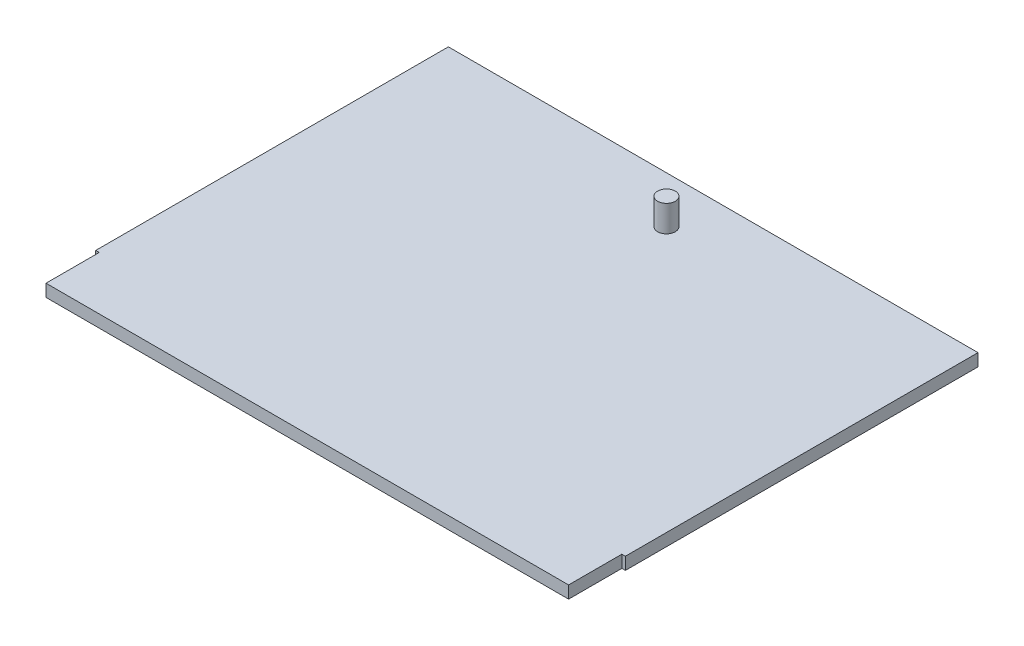
SolidWorks part; units mm, degrees
ref_plane "Front Plane" through (0, 0, 0) normal (0, 0, 1) x (1, 0, 0)
ref_plane "Top Plane" through (0, 0, 0) normal (0, 1, 0) x (1, 0, 0)
ref_plane "Right Plane" through (0, 0, 0) normal (1, 0, 0) x (0, 0, -1)
sketch "Sketch1" plane through (0, 0, 0) normal (0, 1, 0) x (1, 0, 0)
  line L0 (-5.476, 107.7101) -> (-5.476, 7.7101)
  line L1 (-5.476, 107.7101) -> (144.724, 107.7101)
  line L3 (-4.476, -7.3899) -> (143.724, -7.3899)
  line L4 (144.724, 107.7101) -> (144.724, 7.7101)
  line L5 (-5.476, 7.7101) -> (-4.476, 7.7101)
  line L6 (-4.476, 7.7101) -> (-4.476, -7.3899)
  line L8 (144.724, 7.7101) -> (143.724, 7.7101)
  line L9 (143.724, 7.7101) -> (143.724, -7.3899)
  dimension "D1" = 150.2
  dimension "D2" = 100
  dimension "D3" = 100
  dimension "D4" = 1
  dimension "D5" = 1
extrude "Boss-Extrude1" add sketch "Sketch1" along normal blind 3.5
sketch "Sketch2" plane through (0, 3.5, 0) normal (0, 1, 0) x (1, 0, 0)
  circle A0 centre (69.624, 94.4608) radius 2.5
  dimension "D1" = 5
extrude "Boss-Extrude2" add sketch "Sketch2" along normal blind 7.5
